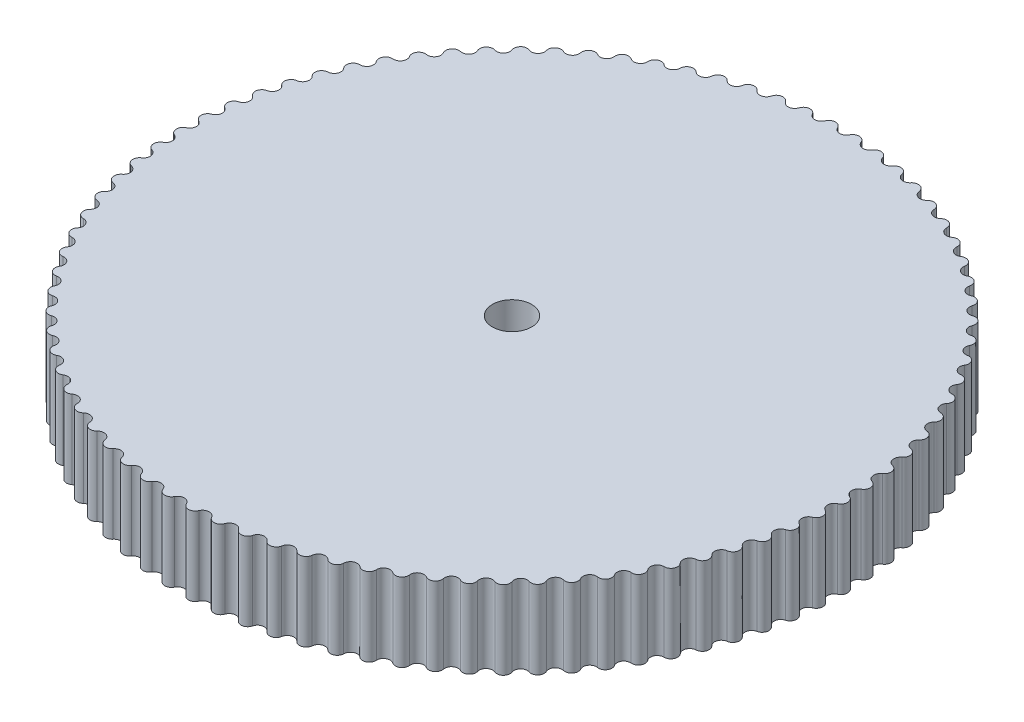
SolidWorks part; units mm, degrees
note: '?' marks a value the reader was unsure of.
ref_plane "Front Plane" through (0, 0, 0) normal (0, 0, 1) x (1, 0, 0)
ref_plane "Top Plane" through (0, 0, 0) normal (0, 1, 0) x (1, 0, 0)
ref_plane "Right Plane" through (0, 0, 0) normal (1, 0, 0) x (0, 0, -1)
sketch "Sketch1" plane through (0, 0, 0) normal (0, 1, 0) x (1, 0, 0)
  line L0 (0, 82) -> (0, 84) construction
  line L1 (3.0661, 81.9427) -> (3.1409, 83.9413) construction
  line L2 (6.1279, 81.7707) -> (6.2773, 83.7651) construction
  line L3 (0, 83) -> (0, 5)
  line L4 (0.3737, 4.986) -> (6.2026, 82.7679)
  circle A0 centre (0, 0) radius 82 construction
  arc A1 (0, 83) -> (3.1035, 82.942) centre (1.5654, 83.7002) ccw
  arc A2 (6.2773, 83.7651) -> (0, 84) centre (0, 0) ccw construction
  arc A3 (3.1035, 82.942) -> (6.2026, 82.7679) centre (4.6149, 82.1761) cw
  arc A4 (0.3737, 4.986) -> (0, 5) centre (0, 0) ccw
  point P6 (0, 83)
  point P9 (3.1035, 82.942)
  dimension "D1" = 164
  dimension "D2" = 2
  dimension "D3" = 10
extrude "Boss-Extrude1" add sketch "Sketch1" along normal blind 20
pattern_circular "CirPattern1" count 84 over 360 about axis through (0, 0, 0) along (0, 1, 0) of "Boss-Extrude1"
ref_axis "Axis1" through (0, 0, 0) along (0, 1, 0)?
sketch "Sketch2" plane through (0, 20, 0) normal (0, 1, 0) x (1, 0, 0)
  line L0 (0, 74.1691) -> (0, -78.0459) construction
  line L1 (19.05, 12.7) -> (26.67, 12.7)
  line L2 (19.05, 12.7) -> (19.05, -12.7)
  line L3 (19.05, -12.7) -> (26.67, -12.7)
  line L4 (26.67, 12.7) -> (26.67, -12.7)
  line L5 (-26.67, 12.7) -> (-26.67, -12.7)
  line L6 (-19.05, -12.7) -> (-26.67, -12.7)
  line L7 (-19.05, 12.7) -> (-19.05, -12.7)
  line L8 (-19.05, 12.7) -> (-26.67, 12.7)
  point P6 (19.05, 0)
  point P12 (-19.05, 0)
  dimension "D1" = 7.62
  dimension "D2" = 25.4
  dimension "D3" = 19.05
